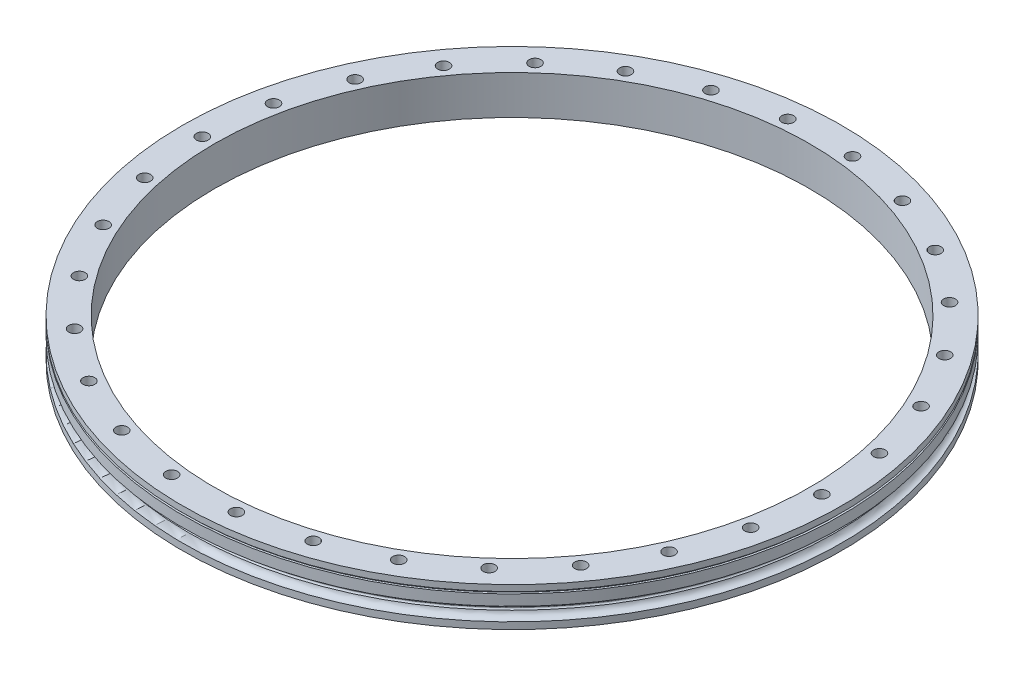
SolidWorks part; units mm, degrees
ref_plane "Plan de face" through (0, 0, 0) normal (0, 0, 1) x (1, 0, 0)
ref_plane "Plan de dessus" through (0, 0, 0) normal (0, 1, 0) x (1, 0, 0)
ref_plane "Plan de droite" through (0, 0, 0) normal (1, 0, 0) x (0, 0, -1)
sketch "Esquisse1" plane through (0, 0, 0) normal (0, 0, 1) x (1, 0, 0)
  line L0 (0, 0) -> (-539.2, 0) construction
  line L1 (-539.2, 0) -> (-539.2, 58) construction
  line L2 (-539.2, 58) -> (0, 58) construction
  line L3 (0, 58) -> (0, 0) construction
  line L4 (-539.2, 0) -> (-492.5, 0) construction
  line L5 (-492.5, 0) -> (-492.5, 10) construction
  line L6 (-492.5, 10) -> (-492.5, 30) construction
  line L7 (-492.5, 58) -> (-492.5, 42.7532) construction
  line L8 (-492.5, 58) -> (-539.2, 58) construction
  line L9 (-492.5, 20) -> (-502, 20) construction
  line L10 (-502, 20) -> (-504, 20) construction
  line L11 (-490.5, 58) -> (-490.5, 49)
  line L12 (-490.5, 49) -> (-487.5, 49)
  line L13 (-487.5, 49) -> (-487.5, 46)
  line L14 (-492.5, 58) -> (-492.5, 30) construction
  line L15 (-492.5, 42.7532) -> (-492.5, 58) construction
  line L16 (-491.5, 58) -> (-491.5, 0) construction
  line L17 (-490.5, 30) -> (-490.5, 58) construction
  line L18 (-490.5, 58) -> (-443, 58)
  line L19 (-443, 58) -> (-443, 0)
  line L20 (-443, 0) -> (-490.5, 0)
  line L21 (-487.5, 46) -> (-490.5, 46)
  line L22 (-490.5, 46) -> (-490.5, 30)
  line L23 (-490.5, 0) -> (-490.5, 10)
  line L24 (-490.5, 46) -> (-492.5, 46) construction
  line L25 (-492.5, 46) -> (-539.2, 46) construction
  line L26 (-539.2, 46) -> (-539.2, -21) construction
  line L27 (-492.5, 58) -> (-490.5, 58) construction
  line L28 (-539.2, -21) -> (-492.5, -21) construction
  line L30 (-492.5, 0) -> (-492.5, -3) construction
  line L31 (-492.5, -3) -> (-495.5, -3) construction
  line L32 (-495.5, -3) -> (-495.5, 0) construction
  line L33 (-495.5, 0) -> (-492.5, 0) construction
  line L34 (-492.5, 0) -> (-492.5, -21) construction
  arc A0 (-492.5, 30) -> (-492.5, 10) centre (-492.5, 20) ccw construction
  arc A1 (-502.3026, 21.977) -> (-502.3026, 18.023) centre (-502, 20) ccw construction
  arc A2 (-502.3026, 18.023) -> (-492.5, 10) centre (-492.5, 20) ccw construction
  arc A3 (-492.5, 30) -> (-502.3026, 21.977) centre (-492.5, 20) ccw construction
  arc A4 (-480.6974, 21.977) -> (-480.6974, 18.023) centre (-481, 20) cw
  arc A5 (-490.5, 30) -> (-490.5, 10) centre (-490.5, 20) cw construction
  arc A6 (-490.5, 30) -> (-480.6974, 21.977) centre (-490.5, 20) cw
  arc A7 (-480.6974, 18.023) -> (-490.5, 10) centre (-490.5, 20) cw
  dimension "D7" = 10
  dimension "D8" = 9.5
  dimension "D9" = 2
  dimension "D2" = 3
  dimension "D3" = 20
  dimension "D4" = 3
  dimension "D5" = 981
  dimension "D6" = 58
  dimension "D10" = 12
  dimension "D11" = 1
  dimension "D12" = 3
  dimension "D13" = 3
  dimension "D14" = 67
  dimension "D15" = 886
  dimension "D17" = 539.2
revolve "Révolution1" add sketch "Esquisse1" angle 360 about L3
sketch "Esquisse4" plane through (0, 58, 0) normal (0, 1, 0) x (1, 0, 0)
  line L0 (0, 0) -> (-461, 0) construction
  circle A0 centre (-461, 0) radius 8.75
  point P38 (0, 0)
  dimension "D1" = 17.5
  dimension "D2" = 461
extrude "Enlèv. mat.-Extru.2" cut sketch "Esquisse4" against normal through all
ref_axis "Axe2" through (0, 45.15, 0) along (0, -1, 0)
pattern_circular "Répétition circulaire1" count 30 over 360 about axis through (0, 45.15, 0) along (0, -1, 0) of "Enlèv. mat.-Extru.2"
